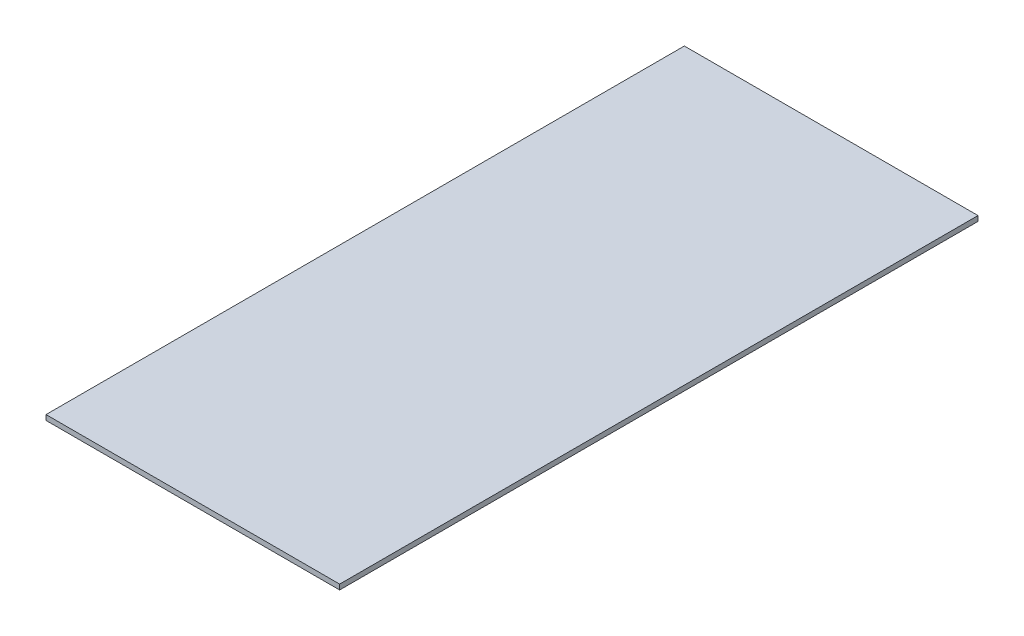
SolidWorks part; units mm, degrees
material "Glass"
ref_plane "Front Plane" through (0, 0, 0) normal (0, 0, 1) x (1, 0, 0)
ref_plane "Top Plane" through (0, 0, 0) normal (0, 1, 0) x (1, 0, 0)
ref_plane "Right Plane" through (0, 0, 0) normal (1, 0, 0) x (0, 0, -1)
sketch "Sketch1" plane through (0, 0, 0) normal (0, 1, 0) x (1, 0, 0)
  line L1 (-230, -500) -> (230, -500)
  line L2 (-230, -500) -> (-230, 500)
  line L3 (-230, 500) -> (230, 500)
  line L4 (230, -500) -> (230, 500)
  line L5 (-230, -500) -> (230, 500) construction
  line L6 (-230, 500) -> (230, -500) construction
  point P0 (0, 0)
  dimension "D1" = 1000
  dimension "D2" = 460
extrude "Boss-Extrude1" add sketch "Sketch1" along normal mid plane 8
sketch "Sketch2" plane through (0, -4, 0) normal (0, -1, 0) x (1, 0, 0)
  line L6 (18, -380) -> (120, -380)
  line L7 (18, -380) -> (18, -75)
  line L9 (120, -380) -> (120, -75)
  line L11 (0, 0) -> (0, 400) construction
  line L12 (69, 568.5637) -> (69, -380) construction
  line L13 (69, -195.1) -> (69, -192.9) construction
  line L14 (18, -75) -> (120, -75)
  line L17 (-6, 400) -> (144, 400)
  line L18 (-6, 400) -> (-6, 110)
  line L19 (-6, 110) -> (144, 110)
  line L20 (144, 400) -> (144, 110)
  line L21 (-6, 400) -> (144, 110) construction
  line L22 (-6, 110) -> (144, 400) construction
  point P1 (69, 255)
  dimension "D1" = 380
  dimension "D2" = 120
  dimension "D3" = 75
  dimension "D4" = 102
  dimension "D5" = 400
  dimension "D6" = 150
  dimension "D7" = 110
split line "Split Line1"
